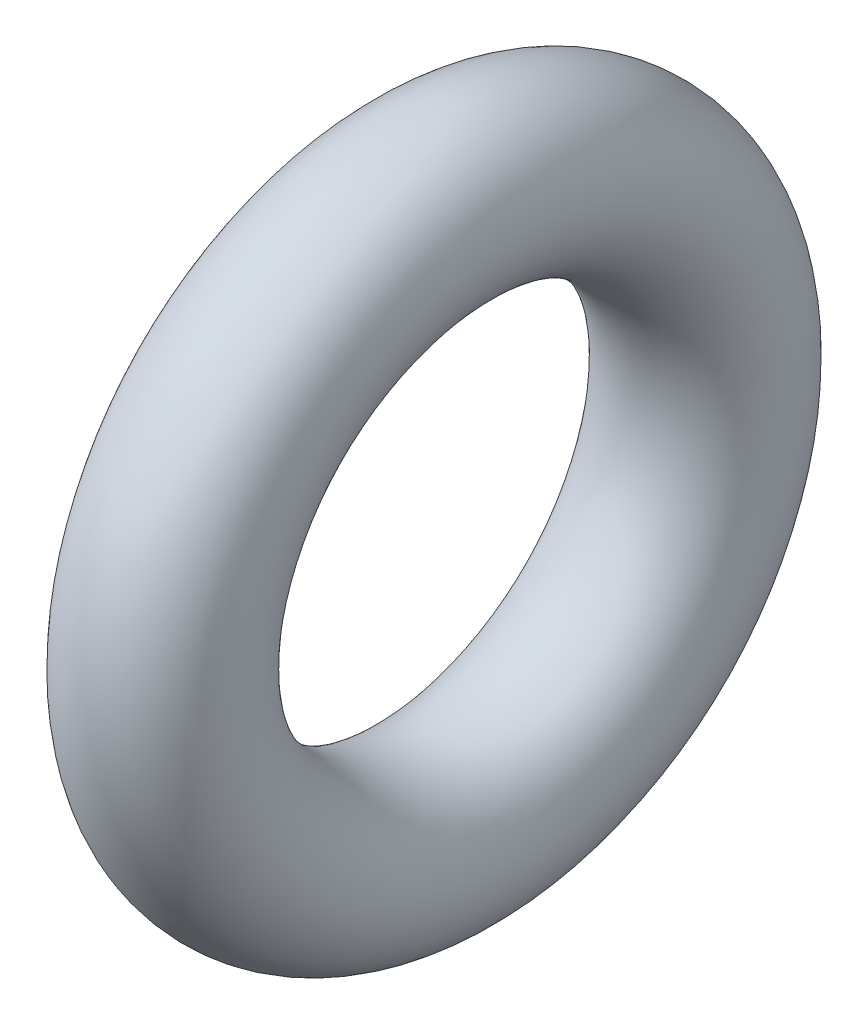
SolidWorks part; units mm, degrees
material "Gummi"
ref_plane "Ebene vorne" through (0, 0, 0) normal (0, 0, 1) x (1, 0, 0)
ref_plane "Ebene oben" through (0, 0, 0) normal (0, 1, 0) x (1, 0, 0)
ref_plane "Ebene rechts" through (0, 0, 0) normal (1, 0, 0) x (0, 0, -1)
ref_axis "Achse1" through (1.375, 0, 0) along (-1, 0, 0)
sketch "Skizze1" plane through (0, 0, 0) normal (0, 0, 1) x (1, 0, 0)
  line L0 (0, 4.3) -> (0, 0) construction
  line L7 (-5.5188, 0) -> (-49.9899, 0) construction
  circle A0 centre (0, 4.3) radius 1.3
  point P3 (0, 5.6)
  point P6 (0, 3)
  dimension "D2" = 2.6
  dimension "D1" = 6
revolve "Rotation1" add sketch "Skizze1" angle 360 about L7
